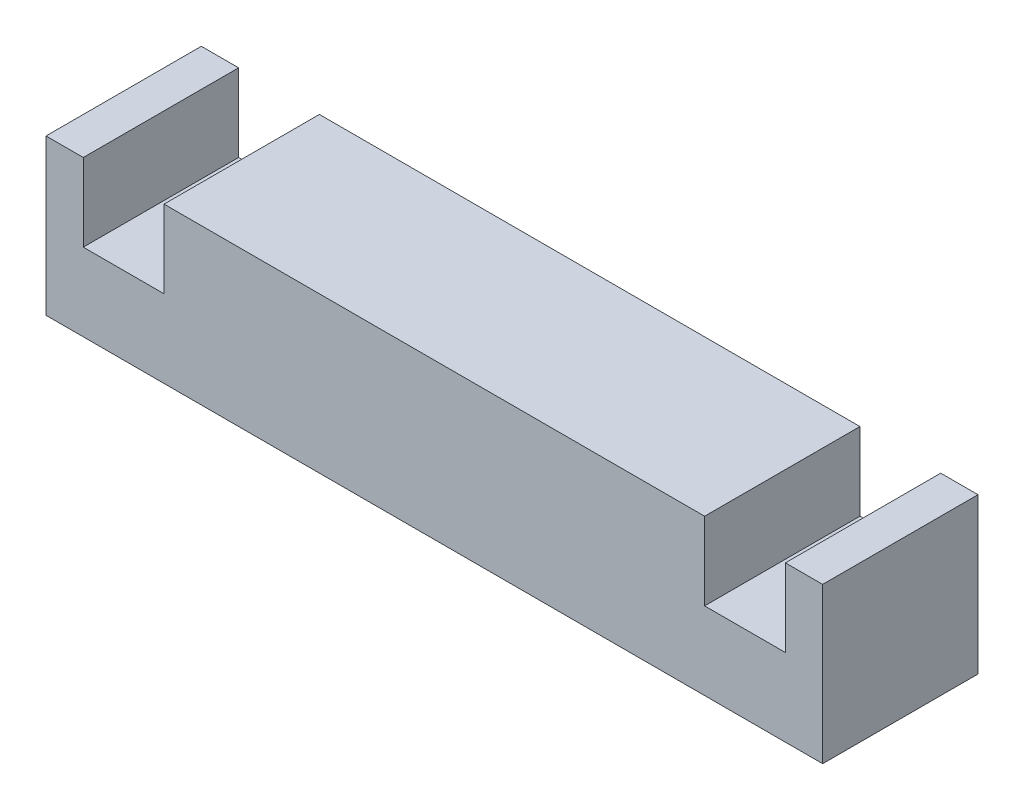
SolidWorks part; units mm, degrees
ref_plane "Front Plane" through (0, 0, 0) normal (0, 0, 1) x (1, 0, 0)
ref_plane "Top Plane" through (0, 0, 0) normal (0, 1, 0) x (1, 0, 0)
ref_plane "Right Plane" through (0, 0, 0) normal (1, 0, 0) x (0, 0, -1)
sketch "Sketch1" plane through (0, 0, 0) normal (0, 0, 1) x (1, 0, 0)
  line L1 (-25, -5) -> (25, -5)
  line L2 (-25, -5) -> (-25, 5)
  line L3 (-25, 5) -> (25, 5)
  line L4 (25, -5) -> (25, 5)
  line L5 (-25, -5) -> (25, 5) construction
  line L6 (-25, 5) -> (25, -5) construction
  point P0 (0, 0)
  dimension "D1" = 50
  dimension "D2" = 10
extrude "Boss-Extrude1" add sketch "Sketch1" along normal blind 10
hole_wizard "M4x0.7 Tapped Hole1" positions "Sketch2" profile "Sketch3" tap size "M4x0.7" standard "ANSI Metric"
sketch "Sketch2" plane through (0, 0, 0) normal (0, 0, -1) x (-1, 0, 0)
  line L0 (-15, 0) -> (15, 0)
  point P0 (-15, 0)
  point P1 (15, 0)
  point P5 (0, 0)
  dimension "D1" = 30
sketch "Sketch3" plane through (15, 0, 0) normal (1, 0, 0) x (0, 1, 0)
  line L0 (0, 0) -> (0, 8.9914)
  line L1 (0, 8.9914) -> (1.65, 8)
  line L2 (1.65, 8) -> (1.65, 0)
  line L5 (1.65, 0) -> (0, 0)
  line L10 (0, 8.9914) -> (-1.65, 8) construction
  line L11 (0, -6.35) -> (0, 107.95) construction
  dimension "Tap Drill Dia." = 3.3
  dimension "Tap Drill Depth" = 8
  dimension "Drill Angle" = 118
cosmetic thread "Hole Thread1" parameters "D1"=4.13, "D2"=4
cosmetic thread "Hole Thread2" parameters "D1"=4.13, "D2"=4
hole_wizard "M3x0.5 Tapped Hole1" positions "Sketch4" profile "Sketch5" tap size "M3x0.5" standard "ANSI Metric" end condition through all
sketch "Sketch4" plane through (0, 5, 0) normal (0, 1, 0) x (1, 0, 0)
  line L0 (-20, -5) -> (20, -5)
  line L2 (25, 0) -> (-25, 0) construction
  point P1 (-20, -5)
  point P2 (20, -5)
  point P7 (0, -5)
  dimension "D1" = 40
  dimension "D2" = 5
cosmetic thread "Hole Thread3" parameters "D2"=3
cosmetic thread "Hole Thread4" parameters "D2"=3
sketch "Sketch5" plane through (-20, 5, 5) normal (1, 0, 0) x (0, 0, 1)
  line L0 (0, 0) -> (0, 10)
  line L1 (0, 10) -> (1.25, 10)
  line L2 (1.25, 10) -> (1.25, 0)
  line L5 (1.25, 0) -> (0, 0)
  line L11 (0, -6.35) -> (0, 107.95) construction
  dimension "Thru Tap Drill Dia." = 2.5
  dimension "Thru Tap Drill Depth" = 10
sketch "Sketch6" plane through (0, 0, 10) normal (0, 0, 1) x (1, 0, 0)
  line L0 (25, 5) -> (-25, 5) construction
  line L1 (-22.6, 0) -> (-17.4, 0)
  line L2 (-22.6, 0) -> (-22.6, 5)
  line L3 (-22.6, 5) -> (-17.4, 5)
  line L4 (-17.4, 0) -> (-17.4, 5)
  line L5 (-22.6, 0) -> (-17.4, 5) construction
  line L6 (-22.6, 5) -> (-17.4, 0) construction
  point P0 (-20, 2.5)
  point P5 (0, 0)
  dimension "D1" = 5.2
  dimension "D2" = 5
  dimension "D3" = 20
extrude "Cut-Extrude1" cut sketch "Sketch6" against normal blind 10
mirror "Mirror1" about plane through (0, 0, 0) normal (1, 0, 0) of "Cut-Extrude1"
